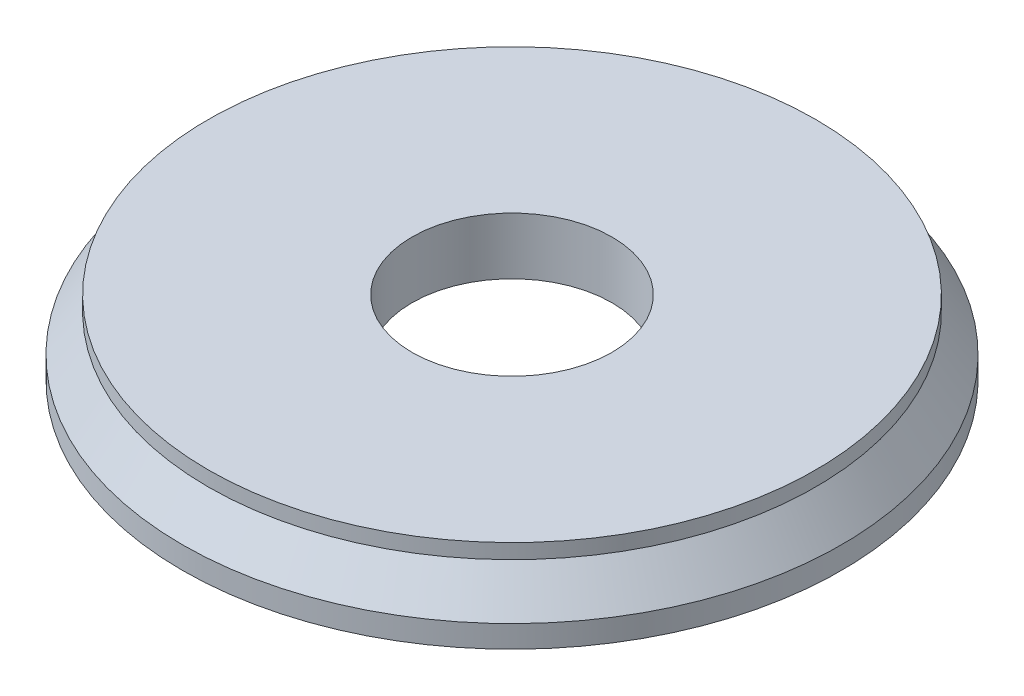
SolidWorks part; units mm, degrees
ref_plane "Плоскость1" through (0, 0, 0) normal (0, 0, 1) x (1, 0, 0)
ref_plane "Плоскость2" through (0, 0, 0) normal (0, 1, 0) x (1, 0, 0)
ref_plane "Плоскость3" through (0, 0, 0) normal (1, 0, 0) x (0, 0, -1)
sketch "Эскиз1" plane through (0, 0, 0) normal (0, 0, 1) x (1, 0, 0)
  line L0 (0, 0) -> (0, 91.3423) construction
  line L1 (13.5, 0) -> (44.5, 0)
  line L2 (44.5, 0) -> (44.5, 3)
  line L3 (44.5, 3) -> (41, 8)
  line L4 (41, 10) -> (41, 8)
  line L5 (41, 10) -> (13.5, 10)
  line L6 (13.5, 0) -> (13.5, 10)
  dimension "D1" = 27
  dimension "D2" = 82
  dimension "D3" = 89
  dimension "D4" = 3
  dimension "D5" = 10
  dimension "D6" = 2
revolve "Повернуть1" add sketch "Эскиз1" angle 360 about L0
cosmetic thread "Условное изображение резьбы1" parameters "D1"=4, "D2"=80
chamfer "Фаска1" distance 4 angle 30 1 edges at (0, 0, -13.5) first distance on face at (0, 0, -44.5)
